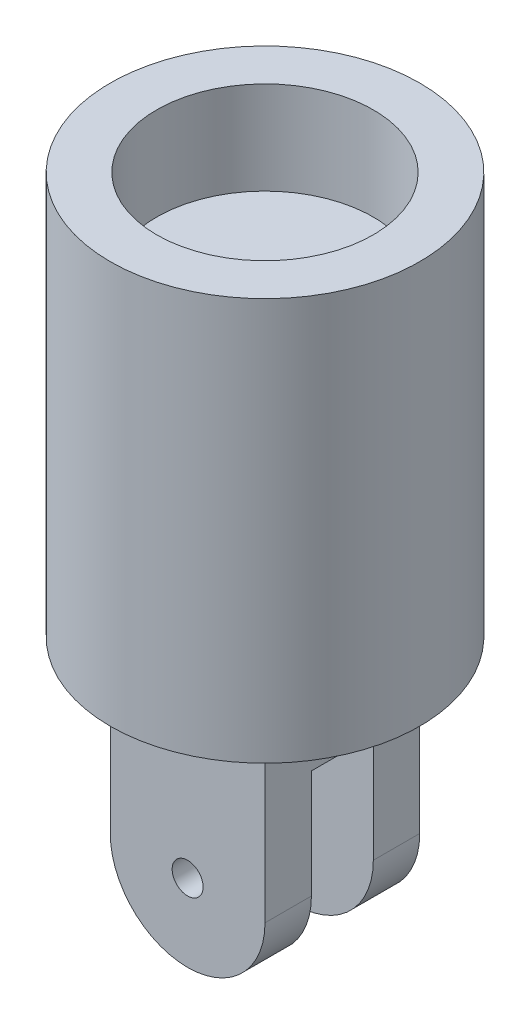
SolidWorks part; units mm, degrees
ref_plane "Front Plane" through (0, 0, 0) normal (0, 0, 1) x (1, 0, 0)
ref_plane "Top Plane" through (0, 0, 0) normal (0, 1, 0) x (1, 0, 0)
ref_plane "Right Plane" through (0, 0, 0) normal (1, 0, 0) x (0, 0, -1)
sketch "Sketch1" plane through (0, 0, 0) normal (0, 1, 0) x (1, 0, 0)
  circle A0 centre (0, 0) radius 5
extrude "Boss-Extrude1" add sketch "Sketch1" along normal blind 13
sketch "Sketch2" plane through (0, 13, 0) normal (0, 1, 0) x (1, 0, 0)
  circle A0 centre (0, 0) radius 3.5
extrude "Cut-Extrude1" cut sketch "Sketch2" against normal blind 3
sketch "Sketch3" plane through (0, 0, 0) normal (0, -1, 0) x (-1, 0, 0)
  line L1 (-2.5, 2.5) -> (2.5, 2.5)
  line L2 (-2.5, 2.5) -> (-2.5, -2.5)
  line L3 (-2.5, -2.5) -> (2.5, -2.5)
  line L4 (2.5, 2.5) -> (2.5, -2.5)
  line L5 (-2.5, 2.5) -> (2.5, -2.5) construction
  line L6 (-2.5, -2.5) -> (2.5, 2.5) construction
  point P0 (0, 0)
  dimension "D1" = 5
  dimension "D2" = 5
extrude "Boss-Extrude2" add sketch "Sketch3" along normal blind 8 contours L2 L3 L4 L1
sketch "Sketch4" plane through (0, -8, 0) normal (0, -1, 0) x (-1, 0, 0)
  line L0 (2.5, 2.5) -> (2.5, -2.5) construction
  line L1 (-2.5, 1) -> (2.5, 1)
  line L2 (-2.5, 1) -> (-2.5, -1)
  line L3 (-2.5, -1) -> (2.5, -1)
  line L4 (2.5, 1) -> (2.5, -1)
  line L5 (-2.5, 1) -> (2.5, -1) construction
  line L6 (-2.5, -1) -> (2.5, 1) construction
  point P0 (0, 0)
  dimension "D1" = 2
  dimension "D2" = 5
extrude "Cut-Extrude2" cut sketch "Sketch4" against normal blind 6
fillet "Fillet2" radius 2.5 4 edges at (-2.5, -8, 1.75) (2.5, -8, 1.75) (2.5, -8, -1.75) (-2.5, -8, -1.75)
sketch "Sketch5" plane through (0, 0, -2.5) normal (0, 0, -1) x (-1, 0, 0)
  circle A0 centre (0, -5.5) radius 0.5
extrude "Cut-Extrude4" cut sketch "Sketch5" against normal through all contours A0
